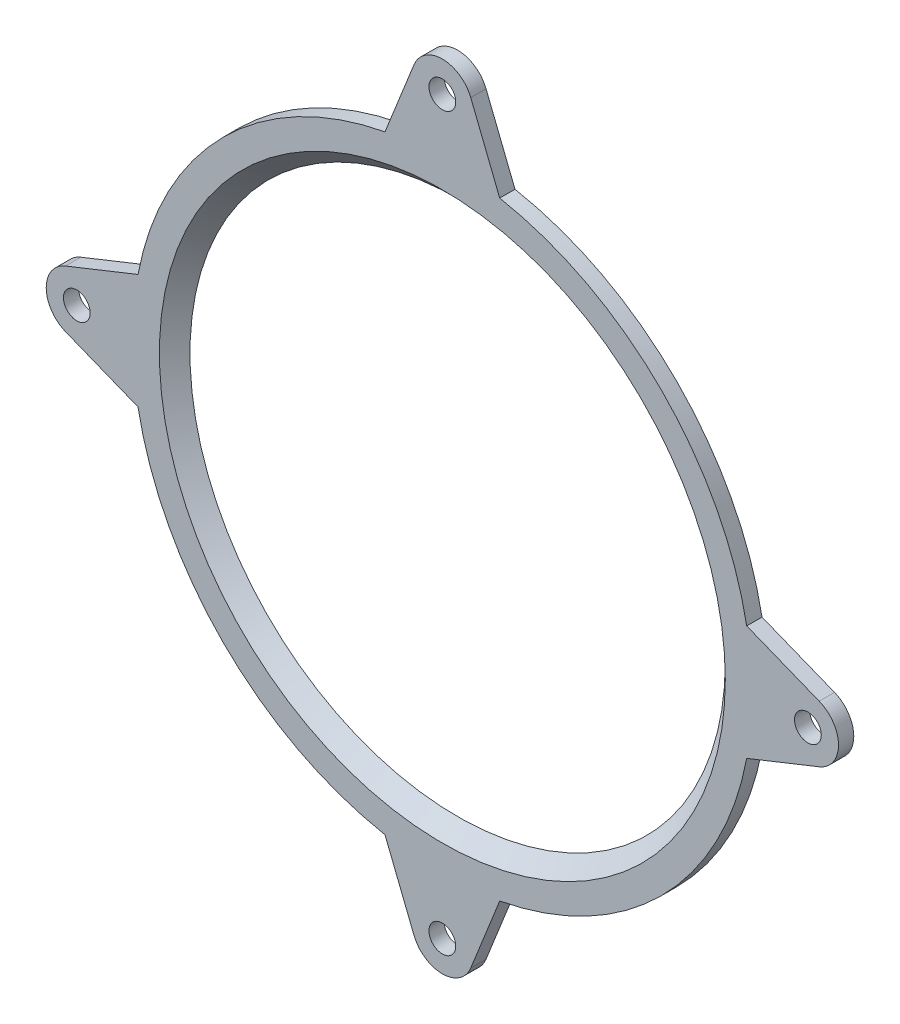
SolidWorks part; units mm, degrees
ref_plane "Front Plane" through (0, 0, 0) normal (0, 0, 1) x (1, 0, 0)
ref_plane "Top Plane" through (0, 0, 0) normal (0, 1, 0) x (1, 0, 0)
ref_plane "Right Plane" through (0, 0, 0) normal (1, 0, 0) x (0, 0, -1)
sketch "Sketch1" plane through (0, 0, 0) normal (0, 0, 1) x (1, 0, 0)
  circle A0 centre (0, 0) radius 35
  circle A1 centre (0, 0) radius 40.5
  dimension "D1" = 70
  dimension "D2" = 5.5
extrude "Boss-Extrude1" add sketch "Sketch1" along normal blind 2
sketch "Sketch2" plane through (0, 0, 0) normal (0, 0, 1) x (1, 0, 0)
  line L0 (0, 47.7995) -> (0, 0) construction
  line L1 (7.5, 39.7995) -> (3.715, 49.2823)
  line L2 (-7.5, 39.7995) -> (-3.715, 49.2823)
  line L3 (-7.5, 39.7995) -> (7.5, 39.7995) construction
  circle A0 centre (0, 0) radius 40.5 construction
  arc A1 (7.5, 39.7995) -> (-7.5, 39.7995) centre (0, 0) ccw
  arc A2 (3.715, 49.2823) -> (-3.715, 49.2823) centre (0, 47.7995) ccw
  circle A3 centre (0, 47.7995) radius 1.75
  dimension "D2" = 8
  dimension "D4" = 3.5
  dimension "D1" = 8
  dimension "D3" = 15
extrude "Boss-Extrude2" add sketch "Sketch2" along normal blind 2
pattern_circular "CirPattern1" count 4 over 360 about axis through (0, 0, 2) along (0, 0, 1) of "Boss-Extrude2"
chamfer "Chamfer1" distance 2 angle 45 1 edges at (35, 0, 2)
